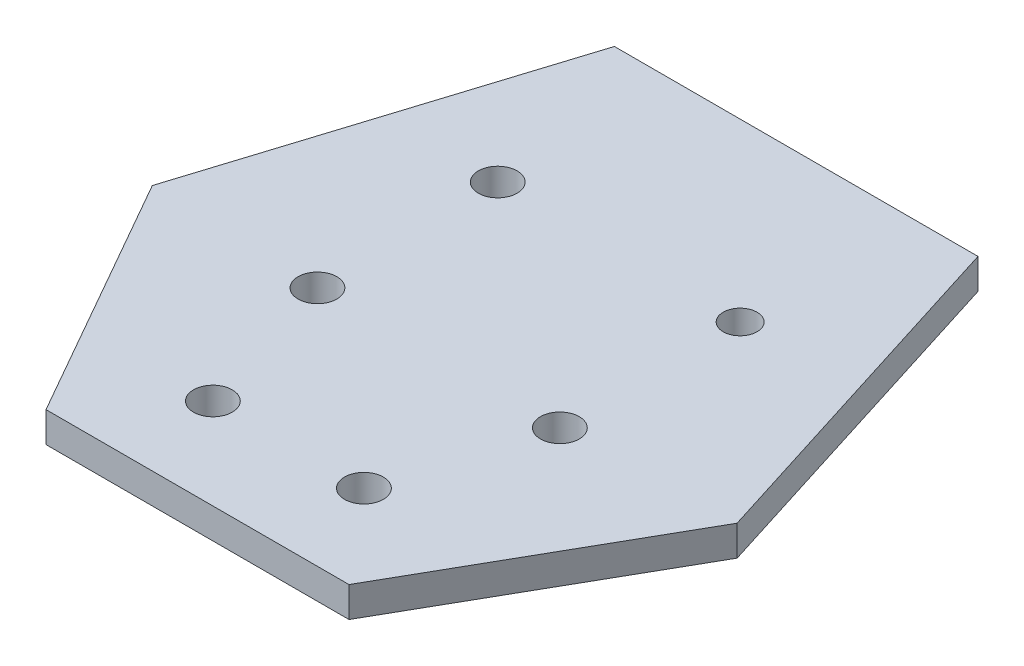
SolidWorks part; units mm, degrees
ref_plane "Front Plane" through (0, 0, 0) normal (0, 0, 1) x (1, 0, 0)
ref_plane "Top Plane" through (0, 0, 0) normal (0, 1, 0) x (1, 0, 0)
ref_plane "Right Plane" through (0, 0, 0) normal (1, 0, 0) x (0, 0, -1)
sketch "Sketch1" plane through (0, 0, 0) normal (0, 1, 0) x (1, 0, 0)
  line L0 (0, 0) -> (-11.5888, -36.83)
  line L13 (-11.5888, -36.83) -> (9.525, -48.5193) construction
  line L15 (-69.987, -36.83) -> (-11.5888, -36.83) construction
  line L17 (49.6887, -36.83) -> (38.1, 0)
  line L18 (38.1, 0) -> (0, 0)
  line L24 (3.4504, -62.7341) -> (35.2004, -62.7341) construction
  line L28 (-11.5888, -36.83) -> (3.175, -62.7341)
  line L30 (3.175, -62.7341) -> (34.925, -62.7341)
  line L32 (34.925, -62.7341) -> (49.6887, -36.83)
  point P2 (6.635, -60.9816)
  point P7 (3.4504, -62.7341)
  point P8 (35.2004, -62.7341)
  point P9 (33.802, -61.9598)
  point P10 (-11.5888, -36.83)
  dimension "D1" = 38.1
  dimension "D2" = 31.75
extrude "Boss-Extrude1" add sketch "Sketch1" along normal mid plane 3.175
sketch "Sketch2" plane through (0, 1.5875, 0) normal (0, 1, 0) x (1, 0, 0)
  line L8 (3.175, -62.7341) -> (34.925, -62.7341) construction
  line L9 (19.05, -62.7341) -> (19.05, 0) construction
  line L10 (38.1, 0) -> (0, 0) construction
  circle A0 centre (31.5913, -18.415) radius 1.778
  circle A1 centre (6.1913, -18.415) radius 2.032
  circle A2 centre (6.35, -37.465) radius 2.032
  circle A3 centre (31.75, -37.465) radius 2.032
  circle A7 centre (11.1357, -53.2091) radius 2.032
  circle A9 centre (26.9643, -53.2091) radius 2.032
  dimension "D1" = 3.556
  dimension "D2" = 9.525
  dimension "D3" = 4.064
  dimension "D5" = 4.064
  dimension "D4" = 7.9607
extrude "Cut-Extrude1" cut sketch "Sketch2" against normal through all
